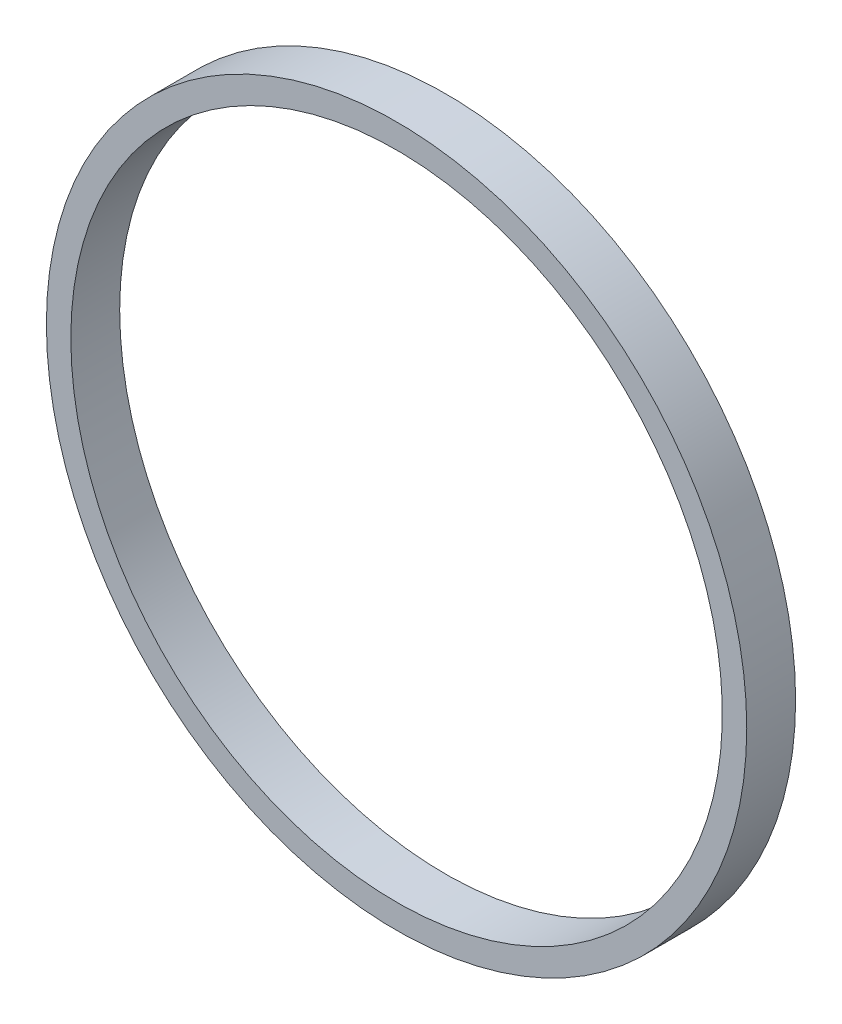
SolidWorks part; units mm, degrees
material "Copper"
ref_plane "Front Plane" through (0, 0, 0) normal (0, 0, 1) x (1, 0, 0)
ref_plane "Top Plane" through (0, 0, 0) normal (0, 1, 0) x (1, 0, 0)
ref_plane "Right Plane" through (0, 0, 0) normal (1, 0, 0) x (0, 0, -1)
sketch "Sketch1" plane through (0, 0, 0) normal (0, 0, 1) x (1, 0, 0)
  circle A0 centre (0, 0) radius 136.525
  circle A1 centre (0, 0) radius 127
extrude "Boss-Extrude1" add sketch "Sketch1" along normal blind 19.05
